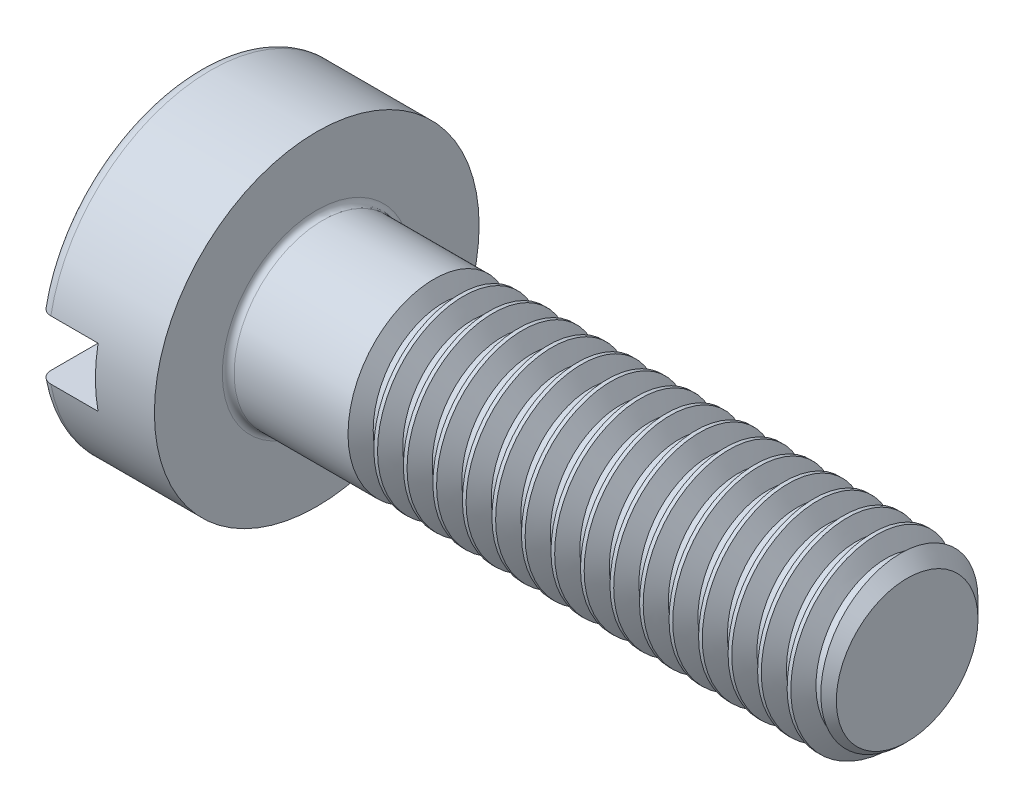
SolidWorks part; units mm, degrees
ref_plane "前视基准面" through (0, 0, 0) normal (0, 0, 1) x (1, 0, 0)
ref_plane "上视基准面" through (0, 0, 0) normal (0, 1, 0) x (1, 0, 0)
ref_plane "右视基准面" through (0, 0, 0) normal (1, 0, 0) x (0, 0, -1)
sketch "草图1" plane through (0, 0, 0) normal (1, 0, 0) x (0, 0, -1)
  circle A0 centre (0, 0) radius 2.75
extrude "拉伸1" add sketch "草图1" along normal blind 2
sketch "草图2" plane through (0, 0, 0) normal (-1, 0, 0) x (0, 0, 1)
  circle A0 centre (0, 0) radius 2.75
  dimension "D1" = 5.5
sketch "草图4" plane through (2, 0, 0) normal (1, 0, 0) x (0, 0, -1)
  circle A0 centre (0, 0) radius 1.5
  dimension "D1" = 3
extrude "拉伸2" add sketch "草图4" along normal blind 10
chamfer "倒角1" distance 0.3 angle 45 1 edges at (12, 0, -1.5)
sketch "草图5" plane through (0, 0, 0) normal (0, 1, 0) x (1, 0, 0)
  line L0 (217.2267, 1.5) -> (226.9644, 1.5) construction
  line L1 (11.7, 1.5) -> (2, 1.5) construction
  line L2 (12, 12.6777) -> (12, 22.4507) construction
  line L3 (12, -1.2) -> (12, 1.2) construction
  line L4 (11.9375, 1.2294) -> (11.7812, 1.5)
  line L5 (12.0625, 1.2294) -> (12.2187, 1.5)
  line L6 (11.7812, 1.5) -> (12.2187, 1.5)
  line L7 (11.9375, 1.2294) -> (12.0625, 1.2294)
  dimension "D1" = 30
  dimension "D2" = 30
  dimension "D3" = 0.4375
  dimension "D4" = 0.125
sketch "草图6" plane through (12, 0, 0) normal (1, 0, 0) x (0, 0, -1)
  circle A0 centre (0, 0) radius 1.5
  dimension "D1" = 3
curve "螺旋线1" pitch 0.5 height 8 radius 1.5 centre (12, 0, 0) axis (-1, 0, 0) start towards (0, 0, -1)
sweep "切除-扫描1" cut profiles "草图5" path "螺旋线1"
fillet "圆角1" radius 0.1 1 edges at (2, 0, -1.5) type face fillet first side face at (2, 0, -1.5) second side face at (2, 0, -2.75)
sketch "草图8" plane through (0, 0, 0) normal (-1, 0, 0) x (0, 0, 1)
  line L0 (-4.0099, 0) -> (3.5608, 0) construction
  line L1 (-3.2303, 0.5) -> (-0.5, 0.5)
  line L2 (0, 2.9549) -> (0, -2.9905) construction
  line L3 (-0.5, 0.5) -> (-0.5, 1.5)
  line L4 (-0.5, 1.5) -> (0.5, 1.5)
  line L5 (0.5, 1.5) -> (0.5, 0.5)
  line L6 (0.5, 0.5) -> (3.266, 0.5)
  line L7 (0.5, -0.5) -> (3.266, -0.5)
  line L8 (0.5, -1.5) -> (0.5, -0.5)
  line L9 (-0.5, -1.5) -> (0.5, -1.5)
  line L10 (-0.5, -0.5) -> (-0.5, -1.5)
  line L11 (-3.2303, -0.5) -> (-0.5, -0.5)
  line L12 (-3.2303, 0.5) -> (-3.2303, -0.5)
  line L13 (3.266, 0.5) -> (3.266, -0.5)
  dimension "D1" = 1
  dimension "D2" = 0.5
  dimension "D3" = 0.5
  dimension "D4" = 1.5
extrude "切除-拉伸1" cut sketch "草图8" against normal blind 1
fillet "圆角2" radius 0.2 1 edges at (0, 2.75, 0)
fillet "圆角3" radius 0.2 1 edges at (0, -2.75, 0)
